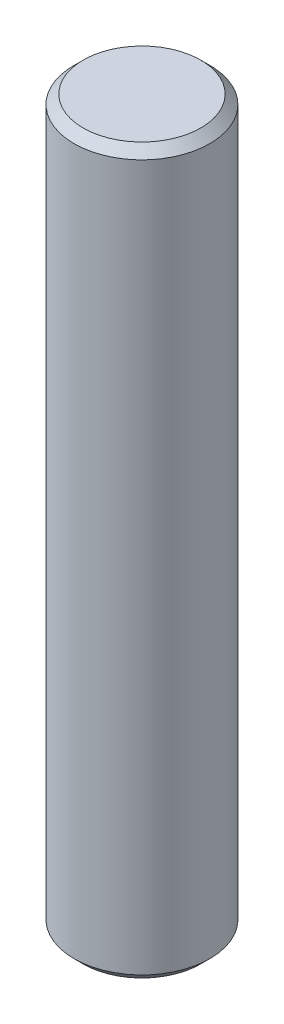
SolidWorks part; units mm, degrees
ref_plane "Front Plane" through (0, 0, 0) normal (0, 0, 1) x (1, 0, 0)
ref_plane "Top Plane" through (0, 0, 0) normal (0, 1, 0) x (1, 0, 0)
ref_plane "Right Plane" through (0, 0, 0) normal (1, 0, 0) x (0, 0, -1)
sketch "Sketch1" plane through (0, 0, 0) normal (0, 1, 0) x (1, 0, 0)
  circle A0 centre (0, 0) radius 0.75
  dimension "D1" = 1.5
extrude "Boss-Extrude1" add sketch "Sketch1" along normal blind 8
chamfer "Chamfer1" distance 0.1 angle 45 2 edges at (0, 0, 0.75) (0, 8, 0.75)
